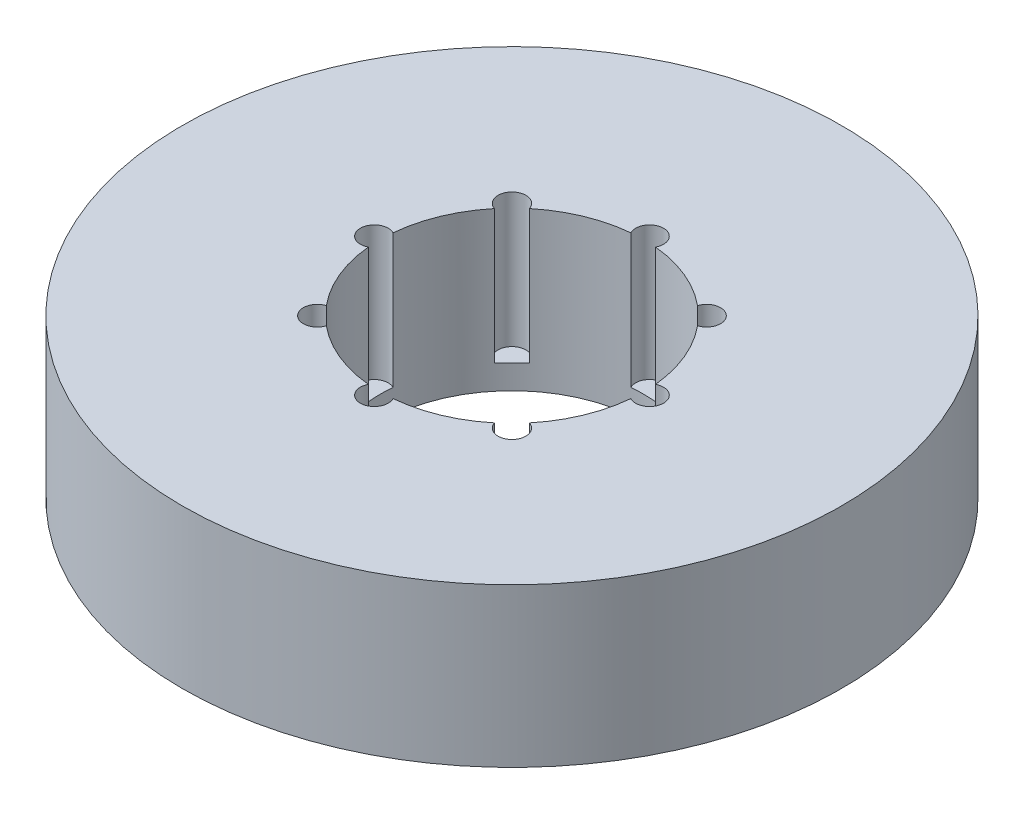
SolidWorks part; units mm, degrees
ref_plane "Front Plane" through (0, 0, 0) normal (0, 0, 1) x (1, 0, 0)
ref_plane "Top Plane" through (0, 0, 0) normal (0, 1, 0) x (1, 0, 0)
ref_plane "Right Plane" through (0, 0, 0) normal (1, 0, 0) x (0, 0, -1)
sketch "Sketch1" plane through (0, 0, 0) normal (0, 1, 0) x (1, 0, 0)
  circle A0 centre (0, 0) radius 62.5
  dimension "FLANGE_OD" = 125
extrude "Boss-Extrude1" add sketch "Sketch1" along normal blind 30
sketch "Sketch2" plane through (0, 0, 0) normal (0, 1, 0) x (1, 0, 0)
  circle A0 centre (0, 0) radius 25
  dimension "BORE_D" = 50
extrude "Cut-Extrude1" cut sketch "Sketch2" along normal through all
sketch "Sketch3" plane through (0, 30, 0) normal (0, 1, 0) x (1, 0, 0)
  circle A0 centre (0, 0) radius 26.1064 construction
  circle A1 centre (-26.1064, 0) radius 2.6404
  dimension "BOLT_D" = 5.2809
  dimension "BOLT_PCD" = 52.2127
extrude "Cut-Extrude2" cut sketch "Sketch3" against normal blind 25.3993
pattern_circular "CirPattern1" count 8 over 360 about axis through (0, 0, 0) along (0, 1, 0) of "Cut-Extrude2"
